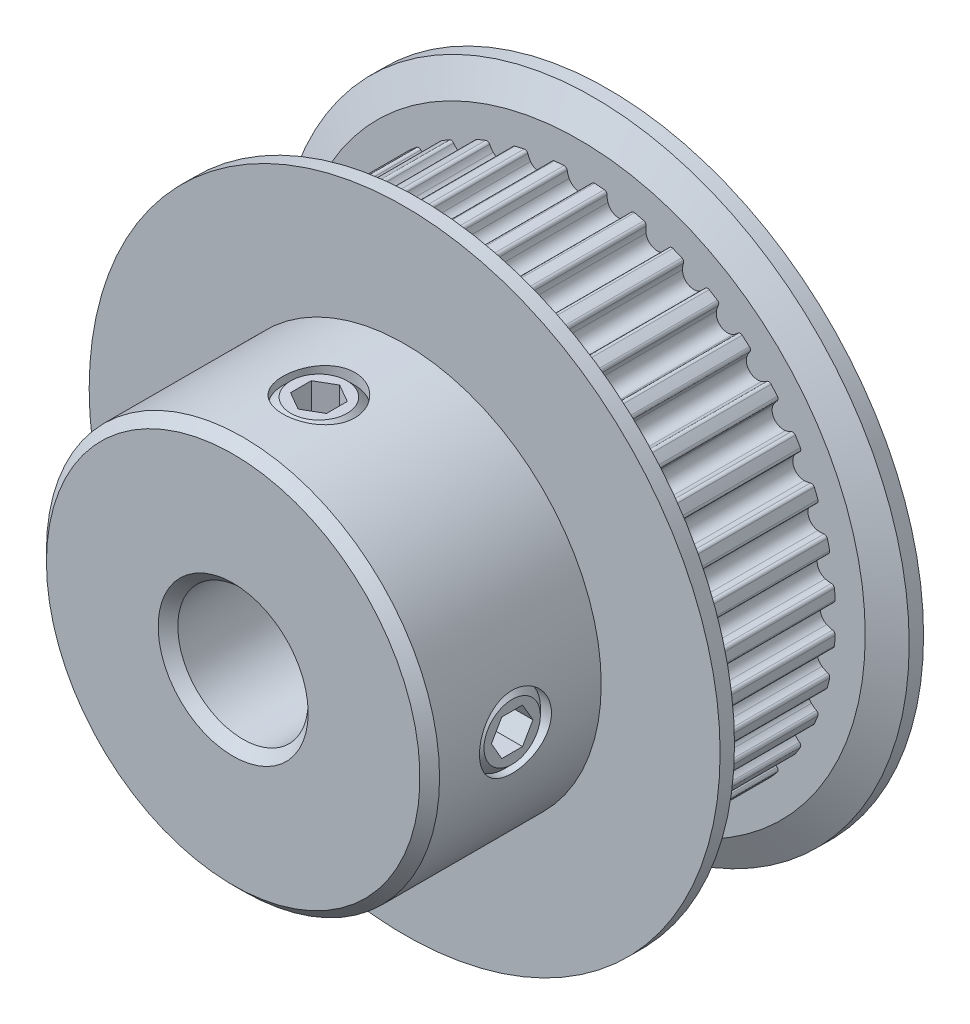
SolidWorks part; units mm, degrees
ref_plane "Front Plane" through (0, 0, 0) normal (0, 0, 1) x (1, 0, 0)
ref_plane "Top Plane" through (0, 0, 0) normal (0, 1, 0) x (1, 0, 0)
ref_plane "Right Plane" through (0, 0, 0) normal (1, 0, 0) x (0, 0, -1)
sketch "Sketch1" plane through (0, 0, 0) normal (0, 0, 1) x (1, 0, 0)
  line L1 (-1.8596, 11.734) -> (1.8596, 11.734) construction
  line L4 (0, 0) -> (0, 11.734) construction
  line L5 (0, 11.734) -> (0, 14.9856) construction
  line L6 (0, 12.738) -> (1.9938, 12.581) construction
  line L7 (1.9938, 12.581) -> (2.8408, 12.4468) construction
  line L8 (1.9938, 12.581) -> (1.8596, 11.734) construction
  line L9 (-1.9938, 12.581) -> (-1.8596, 11.734) construction
  line L10 (-1.9541, 12.3301) -> (-2.4354, 15.367)
  line L11 (-2.4354, 15.367) -> (2.4354, 15.367)
  line L12 (2.4354, 15.367) -> (1.9541, 12.3301)
  circle A0 centre (0, 0) radius 12.738 construction
  circle A1 centre (0, 0) radius 15.367 construction
  circle A2 centre (0, 0) radius 12.484 construction
  arc A3 (-0.4989, 12.0458) -> (0.4989, 12.0458) centre (0, 12.289) ccw
  arc A4 (-0.4989, 12.0458) -> (-0.5887, 12.3344) centre (0.4, 12.484) cw
  arc A5 (-1.9541, 12.3301) -> (-0.746, 12.4617) centre (0, 0) cw
  arc A6 (-0.5887, 12.3344) -> (-0.746, 12.4617) centre (-0.7371, 12.312) ccw
  arc A7 (1.9541, 12.3301) -> (0.746, 12.4617) centre (0, 0) ccw
  arc A8 (0.5887, 12.3344) -> (0.746, 12.4617) centre (0.7371, 12.312) cw
  arc A9 (0.4989, 12.0458) -> (0.5887, 12.3344) centre (-0.4, 12.484) ccw
  point P6 (0, 20.9083)
  point P11 (0, 12.738)
  point P13 (0, 15.367)
  point P14 (0, 12.484)
  dimension "D1" = 5.9227
  dimension "D2" = 2.2476
sketch "Sketch2" plane through (0, 0, 0) normal (1, 0, 0) x (0, 0, -1)
  line L0 (-9.1313, 3.175) -> (9.1313, 3.175)
  line L1 (-9.1313, 3.175) -> (-9.1313, 9.575)
  line L2 (-9.1313, 9.575) -> (-0.7787, 9.575)
  line L3 (-0.7787, 9.575) -> (-0.7787, 15.367)
  line L4 (-0.7787, 15.367) -> (0.6213, 15.367) construction
  line L5 (0.6213, 15.367) -> (0.6213, 12.484) construction
  line L6 (0.6213, 12.484) -> (7.7313, 12.484)
  line L7 (7.7313, 12.484) -> (7.7313, 15.367) construction
  line L8 (7.7313, 15.367) -> (9.1313, 15.367) construction
  line L9 (9.1313, 15.367) -> (9.1313, 3.175)
  line L10 (-9.1313, 0) -> (9.1313, 0) construction
  line L11 (8.4313, 15.367) -> (7.7313, 13.9255)
  line L12 (0.6213, 13.9255) -> (-0.0787, 15.367)
  line L13 (-0.7787, 15.367) -> (-0.0787, 15.367)
  line L14 (0.6213, 13.9255) -> (0.6213, 12.484)
  line L15 (7.7313, 12.484) -> (7.7313, 13.9255)
  line L16 (8.4313, 15.367) -> (9.1313, 15.367)
  arc A0 (0.6213, 13.9255) -> (-0.0787, 15.367) centre (-1.2129, 13.9255) ccw construction
  arc A1 (7.7313, 13.9255) -> (8.4313, 15.367) centre (9.5655, 13.9255) cw construction
  point P12 (0.6213, 13.9255)
  point P14 (-0.0787, 15.367)
  point P20 (7.7313, 13.9255)
  point P21 (8.4313, 15.367)
  point P25 (7.7313, 0)
  point P26 (0.6213, 0)
revolve "Revolve1" add sketch "Sketch2" angle 360 mid plane about L10
sketch "Sketch3" plane through (0, 0, 0) normal (0, 0, 1) x (1, 0, 0)
  line L6 (2.4354, 15.367) -> (-2.4354, 15.367)
  line L7 (1.9541, 12.3301) -> (2.4354, 15.367)
  line L8 (-2.4354, 15.367) -> (-1.9541, 12.3301)
  line L9 (2.4354, 15.367) -> (-2.4354, 15.367)
  line L10 (1.9541, 12.3301) -> (2.4354, 15.367)
  line L11 (-2.4354, 15.367) -> (-1.9541, 12.3301)
  arc A8 (1.9541, 12.3301) -> (0.746, 12.4617) centre (0, 0) ccw
  arc A9 (0.746, 12.4617) -> (0.5887, 12.3344) centre (0.7371, 12.312) ccw
  arc A10 (0.4989, 12.0458) -> (0.5887, 12.3344) centre (-0.4, 12.484) ccw
  arc A11 (-0.4989, 12.0458) -> (0.4989, 12.0458) centre (0, 12.289) ccw
  arc A12 (-0.5887, 12.3344) -> (-0.4989, 12.0458) centre (0.4, 12.484) ccw
  arc A13 (-0.5887, 12.3344) -> (-0.746, 12.4617) centre (-0.7371, 12.312) ccw
  arc A14 (-0.746, 12.4617) -> (-1.9541, 12.3301) centre (0, 0) ccw
  arc A15 (1.9541, 12.3301) -> (0.746, 12.4617) centre (0, 0) ccw
  arc A16 (0.746, 12.4617) -> (0.5887, 12.3344) centre (0.7371, 12.312) ccw
  arc A17 (0.4989, 12.0458) -> (0.5887, 12.3344) centre (-0.4, 12.484) ccw
  arc A18 (-0.4989, 12.0458) -> (0.4989, 12.0458) centre (0, 12.289) ccw
  arc A19 (-0.5887, 12.3344) -> (-0.4989, 12.0458) centre (0.4, 12.484) ccw
  arc A20 (-0.5887, 12.3344) -> (-0.746, 12.4617) centre (-0.7371, 12.312) ccw
  arc A21 (-0.746, 12.4617) -> (-1.9541, 12.3301) centre (0, 0) ccw
  dimension "D1" = 0
extrude "Cut-Extrude1" cut sketch "Sketch3" against normal up to vertex (7.7313 mm away) from vertex up to point (0, 12.484, -7.7313) starting at point (0, 12.484, -0.6213)
pattern_circular "CirPattern1" count 40 over 360 about axis through (0, 0, 9.1313) along (0, 0, 1) of "Cut-Extrude1"
sketch "Sketch4" plane through (0, 0, 0) normal (1, 0, 0) x (0, -1, 0)
  line L0 (0, -0.7787) -> (0, -9.1313) construction
  line L1 (-9.575, -0.7787) -> (9.575, -0.7787) construction
  line L2 (-9.575, -9.1313) -> (9.575, -9.1313) construction
  circle A0 centre (0, -4.955) radius 1.7526
extrude "Cut-Extrude2" cut sketch "Sketch4" along normal through all
ref_plane "Plane1" through (0, 0, 4.955) normal (0, 0, 1) x (1, 0, 0)
sketch "Sketch5" plane through (0, 0, 4.955) normal (0, 0, 1) x (1, 0, 0)
  line L0 (0, 0.1664) -> (0, 9.575) construction
  line L1 (3.175, -1.3716) -> (3.175, 0)
  line L2 (3.556, -1.7526) -> (9.0322, -1.7526)
  line L3 (3.175, 0) -> (9.575, 0) construction
  line L4 (3.175, 0) -> (9.4132, 0)
  line L5 (9.4132, 0) -> (9.4132, -1.3716)
  line L6 (3.556, -1.7526) -> (3.175, -1.3716)
  line L7 (9.4132, -1.3716) -> (9.0322, -1.7526)
  circle A0 centre (0, 0) radius 9.575 construction
  circle A1 centre (0, 0) radius 3.175 construction
  point P2 (3.175, -1.7526)
  point P11 (9.4132, -1.7526)
revolve "Revolve2" add sketch "Sketch5" angle 360 mid plane about L4
sketch "Sketch6" plane through (9.4132, 5.3841, 0) normal (-1, 0, 0) x (0, -1, 0)
  line L1 (5.3841, 5.9669) -> (4.5078, 5.4609)
  line L2 (4.5078, 5.4609) -> (4.5078, 4.4491)
  line L3 (4.5078, 4.4491) -> (5.3841, 3.9431)
  line L4 (5.3841, 3.9431) -> (6.2604, 4.4491)
  line L5 (6.2604, 4.4491) -> (6.2604, 5.4609)
  line L6 (6.2604, 5.4609) -> (5.3841, 5.9669)
  circle A0 centre (5.3841, 4.955) radius 0.8763 construction
  dimension "D1" = 1.7526
extrude "Cut-Extrude3" cut sketch "Sketch6" along normal blind 1.3144
pattern_circular "CirPattern2" count 2 over 90 about axis through (0, 0, 9.1313) along (0, 0, 1) of "Cut-Extrude2", "Revolve2", "Cut-Extrude3"
chamfer "Chamfer1" distance 0.4788 angle 45 2 edges at (3.175, 0, 9.1313) (9.575, 0, 9.1313)
ref_axis "Center Axis 1" through (0, 0, -9.1313) along (0, 0, 1)
ref_plane "Contact Plane 1" through (0, 0, 9.1313) normal (0, 0, 1) x (1, 0, 0)
ref_plane "Contact Plane 2" through (0, 0, -9.1313) normal (0, 0, -1) x (-1, 0, 0)
equation "\"D2@Sketch1\" = \"D1@Sketch1\"/2"
equation "\"D1@Sketch6\" = \"Set Screw@Sketch4\" / 2"
equation "\"D1@Cut-Extrude3\" = \"D1@Sketch6\"*.75"
equation "\"D1@Chamfer1\"=\"Hub Dia@Sketch2\"*.025"
